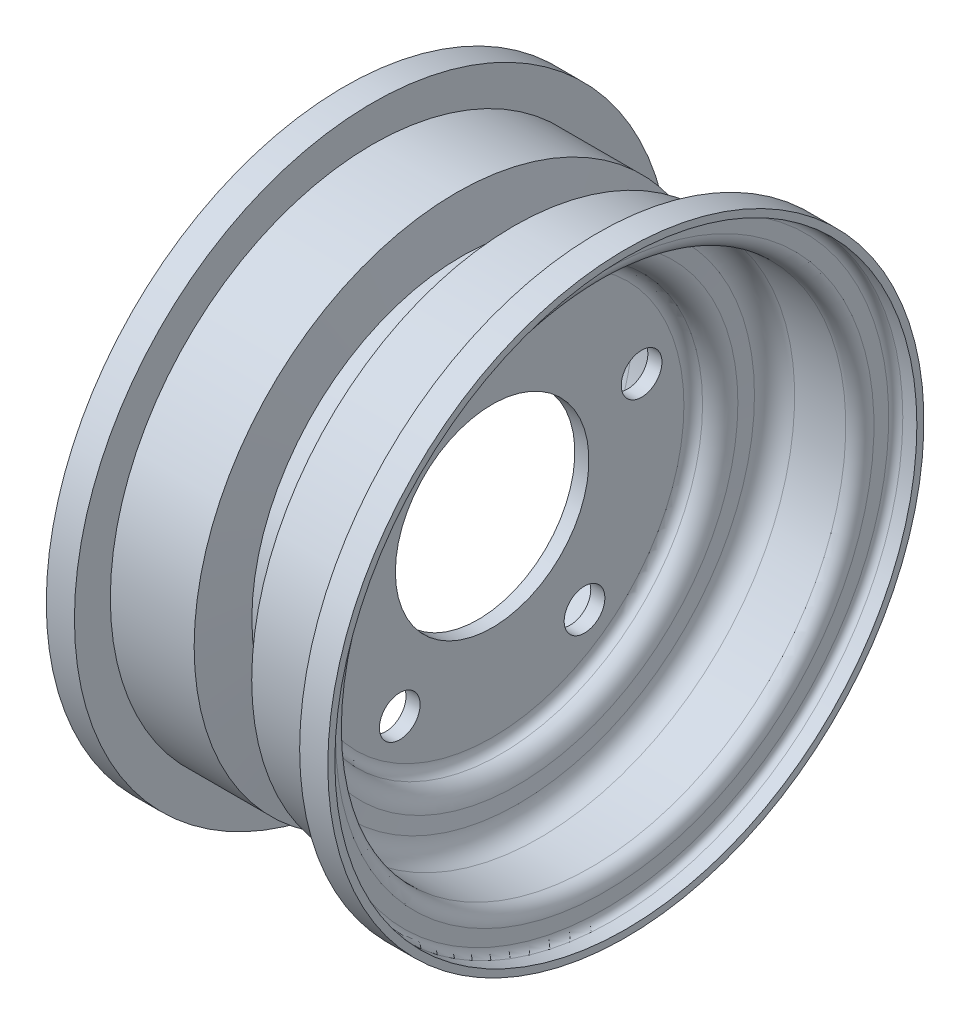
SolidWorks part; units mm, degrees
material "1023 Carbon Steel Sheet (SS)"
ref_plane "Front Plane" through (0, 0, 0) normal (0, 0, 1) x (1, 0, 0)
ref_plane "Top Plane" through (0, 0, 0) normal (0, 1, 0) x (1, 0, 0)
ref_plane "Right Plane" through (0, 0, 0) normal (1, 0, 0) x (0, 0, -1)
sketch "Sketch2" plane through (0, 0, 0) normal (0, 0, 1) x (1, 0, 0)
  line L0 (2.54, 0) -> (2.54, 34.925) construction
  line L1 (2.54, 34.925) -> (2.54, 73.025)
  line L2 (2.54, 73.025) -> (10.922, 73.025)
  line L3 (50.8, 107.569) -> (50.8, 105.029)
  line L4 (12.7, 92.075) -> (43.18, 92.075)
  line L5 (43.18, 92.075) -> (43.18, 105.029)
  line L6 (43.18, 105.029) -> (50.8, 105.029)
  line L7 (10.922, 73.025) -> (12.7, 92.075)
  line L8 (0, 0) -> (2.54, 0) construction
  line L9 (0, 0) -> (0, 213.5492) construction
  line L10 (0, 34.925) -> (0, 75.565)
  line L11 (0, 75.565) -> (8.608, 75.565)
  line L12 (8.608, 75.565) -> (10.386, 94.615)
  line L13 (10.386, 94.615) -> (40.64, 94.615)
  line L14 (40.64, 94.615) -> (40.64, 107.569)
  line L15 (40.64, 107.569) -> (48.26, 107.569)
  line L16 (48.26, 107.569) -> (48.26, 107.569)
  line L17 (0, 34.925) -> (2.54, 34.925)
  line L18 (48.26, 107.569) -> (50.8, 107.569)
  dimension "D1" = 34.925
  dimension "D2" = 38.1
  dimension "D3" = 8.382
  dimension "D4" = 19.05
  dimension "D5" = 2.54
  dimension "D6" = 7.62
  dimension "D7" = 30.48
  dimension "0.51" = 12.954
  dimension "D8" = 2.54
  dimension "D9" = 48.26
  dimension "D10" = 2.54
revolve "Revolve2" add sketch "Sketch2" angle 360 about L8 region at (1.27, 35.8114, 0)
mirror "Mirror1" about plane through (0, 0, 0) normal (1, 0, 0) of "Revolve2"
sketch "Sketch5" plane through (0, 0, 0) normal (1, 0, 0) x (0, 0, -1)
  line L3 (-53.9412, 17.5266) -> (-33.3375, -45.8851) construction
  line L4 (-33.3375, -45.8851) -> (33.3375, -45.8851) construction
  line L5 (33.3375, -45.8851) -> (53.9412, 17.5266) construction
  line L6 (53.9412, 17.5266) -> (0, 56.7171) construction
  line L7 (0, 56.7171) -> (-53.9412, 17.5266) construction
  circle A0 centre (0, 0) radius 56.7171 construction
  point P3 (0, 56.7171)
  point P9 (53.9412, 17.5266)
  point P10 (33.3375, -45.8851)
  point P11 (-33.3375, -45.8851)
  point P12 (-53.9412, 17.5266)
  point P13 (0, 56.7171)
  dimension "D1" = 66.675
hole_wizard "37/64 (0.57813) Diameter Hole1" positions "Sketch6" profile "Sketch7" hole size "37/64" standard "ANSI Inch" end condition through all
sketch "Sketch6" plane through (2.54, 0, 0) normal (1, 0, 0) x (0, 0, -1)
  point P0 (0, 56.7171)
  point P3 (53.9412, 17.5266)
  point P6 (33.3375, -45.8851)
  point P9 (-33.3375, -45.8851)
  point P12 (-53.9412, 17.5266)
sketch "Sketch7" plane through (2.54, 56.7171, 0) normal (0, 1, 0) x (0, 0, -1)
  line L0 (0, 0) -> (0, 53.34)
  line L1 (0, 53.34) -> (7.3423, 53.34)
  line L2 (7.3423, 53.34) -> (7.3423, 0)
  line L5 (7.3423, 0) -> (0, 0)
  line L11 (0, -6.35) -> (0, 107.95) construction
  dimension "Thru Hole Dia." = 14.6845
  dimension "Thru Hole Depth" = 53.34
fillet "Fillet1" radius 3.81 2 edges at (2.54, 0, 73.025) (-2.54, 0, 73.025)
fillet "Fillet2" radius 7.62 4 edges at (12.7, 0, 92.075) (10.922, 0, 73.025) (-12.7, 0, 92.075) (-10.922, 0, 73.025)
fillet "Fillet3" radius 5.08 2 edges at (43.18, 0, 92.075) (-43.18, 0, 92.075)
fillet "Fillet4" radius 2.54 2 edges at (43.18, 0, 105.029) (-43.18, 0, 105.029)
